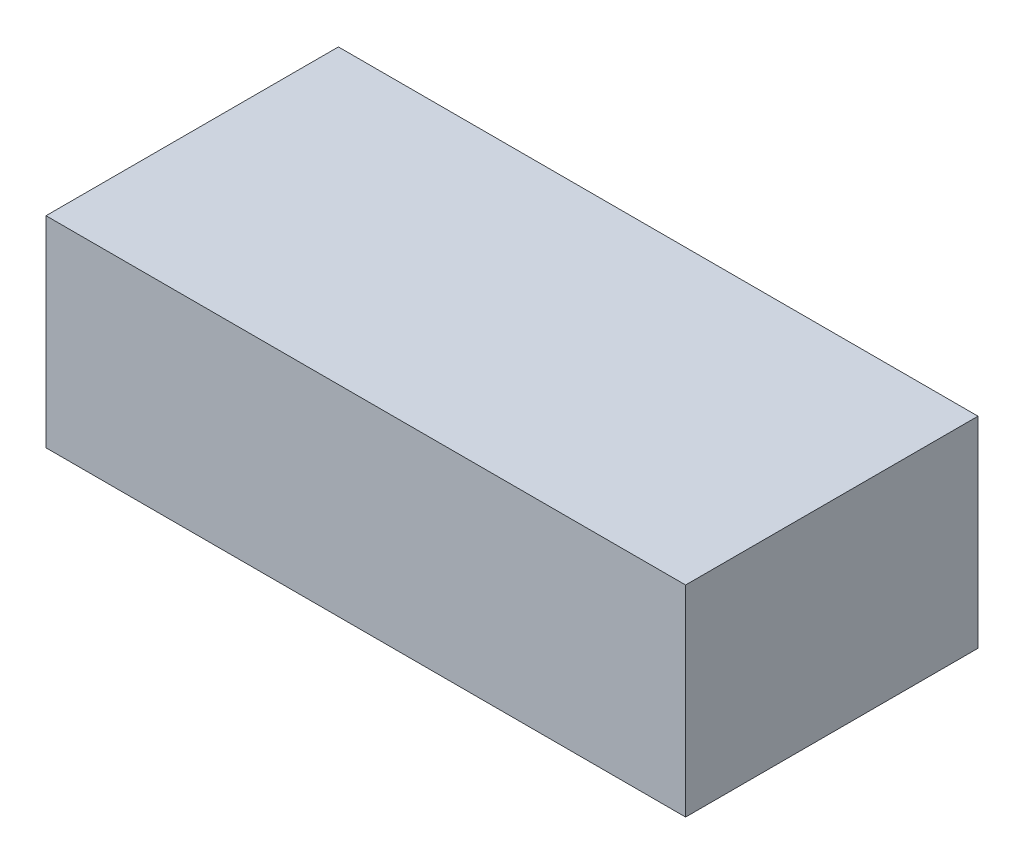
SolidWorks part; units mm, degrees
ref_plane "Front Plane" through (0, 0, 0) normal (0, 0, 1) x (1, 0, 0)
ref_plane "Top Plane" through (0, 0, 0) normal (0, 1, 0) x (1, 0, 0)
ref_plane "Right Plane" through (0, 0, 0) normal (1, 0, 0) x (0, 0, -1)
sketch "Sketch1" plane through (0, 0, 0) normal (0, 1, 0) x (1, 0, 0)
  line L1 (-70, 32) -> (70, 32)
  line L2 (-70, 32) -> (-70, -32)
  line L3 (-70, -32) -> (70, -32)
  line L4 (70, 32) -> (70, -32)
  line L5 (-70, 32) -> (70, -32) construction
  line L6 (-70, -32) -> (70, 32) construction
  point P0 (0, 0)
  dimension "D1" = 64
  dimension "D2" = 140
extrude "Boss-Extrude1" add sketch "Sketch1" along normal blind 44
